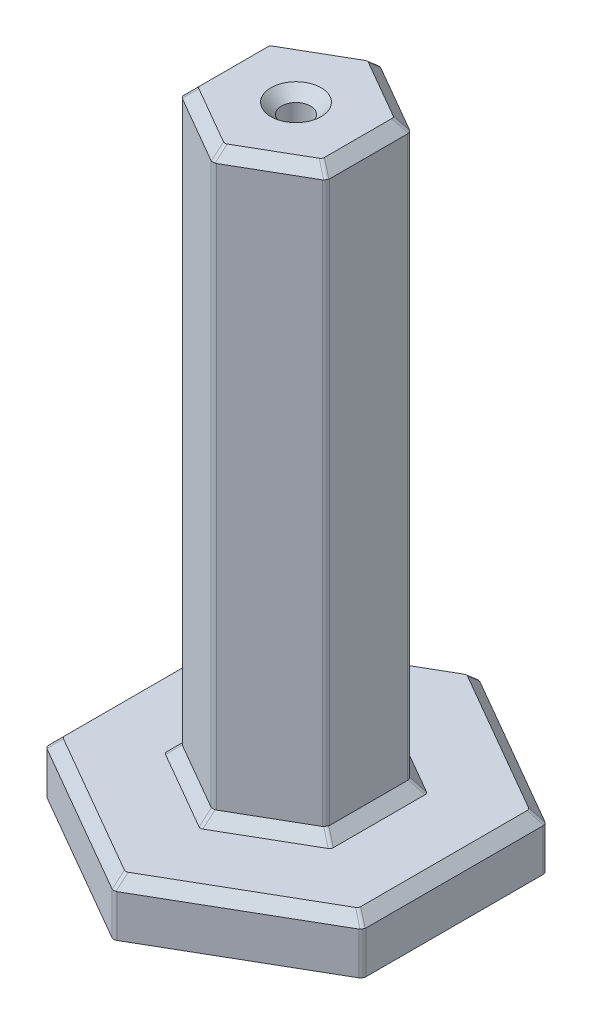
SolidWorks part; units mm, degrees
ref_plane "Front Plane" through (0, 0, 0) normal (0, 0, 1) x (1, 0, 0)
ref_plane "Top Plane" through (0, 0, 0) normal (0, 1, 0) x (1, 0, 0)
ref_plane "Right Plane" through (0, 0, 0) normal (1, 0, 0) x (0, 0, -1)
sketch "Sketch2" plane through (0, 0, 0) normal (0, 1, 0) x (1, 0, 0)
  line L1 (0, -7.9386) -> (6.875, -3.9693)
  line L2 (6.875, -3.9693) -> (6.875, 3.9693)
  line L3 (6.875, 3.9693) -> (0, 7.9386)
  line L4 (0, 7.9386) -> (-6.875, 3.9693)
  line L5 (-6.875, 3.9693) -> (-6.875, -3.9693)
  line L6 (-6.875, -3.9693) -> (0, -7.9386)
  line L7 (0, -17.3205) -> (15, -8.6603)
  line L8 (15, -8.6603) -> (15, 8.6603)
  line L9 (15, 8.6603) -> (0, 17.3205)
  line L10 (0, 17.3205) -> (-15, 8.6603)
  line L11 (-15, 8.6603) -> (-15, -8.6603)
  line L12 (-15, -8.6603) -> (0, -17.3205)
  circle A0 centre (0, 0) radius 6.875 construction
  circle A1 centre (0, 0) radius 15 construction
  dimension "D1" = 13.75
  dimension "D2" = 30
extrude "Boss-Extrude1" add sketch "Sketch2" along normal blind 60 contours L5 L6 L1 L2 L3 L4 region at (0, 0, 0)
extrude "Boss-Extrude2" add sketch "Sketch2<3>" along normal blind 5
sketch "Sketch2<3>" plane through (0, 0, 0) normal (0, 1, 0) x (1, 0, 0) same geometry as "Sketch2"
sketch "Sketch5" plane through (0, 60, 0) normal (0, 1, 0) x (1, 0, 0)
  circle A1 centre (0, 0) radius 1.375
  dimension "D2" = 2.75
extrude "Cut-Extrude2" cut sketch "Sketch5" against normal blind 15 contours A1 region at (0, 60, 0)
chamfer "Chamfer1" distance 1 angle 45 19 edges at (-3.4375, 60, -5.9539) (3.4375, 60, -5.9539) (6.875, 60, 0) (3.4375, 60, 5.9539) (-3.4375, 60, 5.9539) (-6.875, 60, 0) (0, 60, 1.375) (6.875, 5, 0) (3.4375, 5, -5.9539) (-3.4375, 5, -5.9539) (-6.875, 5, 0) (-3.4375, 5, 5.9539) (3.4375, 5, 5.9539) (-15, 5, 0) (-7.5, 5, -12.9904) (7.5, 5, -12.9904) (15, 5, 0) (7.5, 5, 12.9904) (-7.5, 5, 12.9904)
fillet "Fillet2" radius 0.5 30 edges at (6.375, 59.5, 3.6806) (0, 59.5, 7.3612) (-6.375, 59.5, 3.6806) (-6.375, 59.5, -3.6806) (0, 59.5, -7.3612) (6.375, 59.5, -3.6806) (0, 4.5, -16.7432) (-14.5, 4.5, 8.3716) (-14.5, 4.5, -8.3716) (0, 5.5, -8.5159) (-7.375, 5.5, -4.258) (-7.375, 5.5, 4.258) (7.375, 5.5, -4.258) (14.5, 4.5, -8.3716) (14.5, 4.5, 8.3716) (7.375, 5.5, 4.258) (0, 4.5, 16.7432) (0, 5.5, 8.5159) (15, 2, 8.6603) (0, 2, 17.3205) (-15, 2, 8.6603) (15, 2, -8.6603) (0, 2, -17.3205) (-15, 2, -8.6603) (-6.875, 32.5, 3.9693) (-6.875, 32.5, -3.9693) (0, 32.5, -7.9386) (6.875, 32.5, -3.9693) (6.875, 32.5, 3.9693) (0, 32.5, 7.9386)
